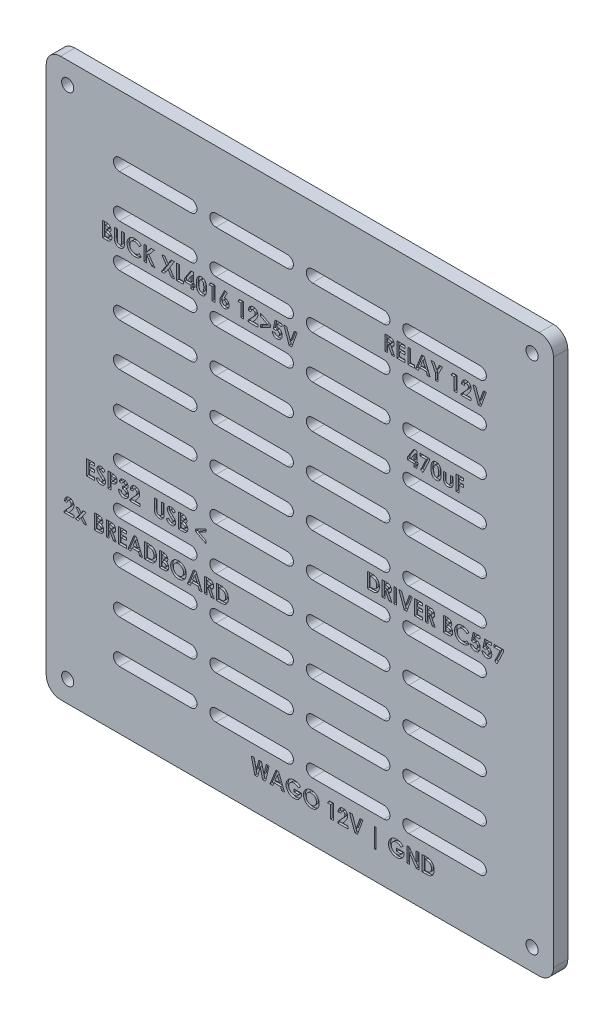
SolidWorks part; units mm, degrees
ref_plane "Front Plane" through (0, 0, 0) normal (0, 0, 1) x (1, 0, 0)
ref_plane "Top Plane" through (0, 0, 0) normal (0, 1, 0) x (1, 0, 0)
ref_plane "Right Plane" through (0, 0, 0) normal (1, 0, 0) x (0, 0, -1)
sketch "Sketch1" plane through (0, 0, 0) normal (0, 0, 1) x (1, 0, 0)
  line L0 (-67, 40) -> (67, 40)
  line L1 (71, 44) -> (71, 192)
  line L2 (67, 196) -> (-67, 196)
  line L3 (-71, 192) -> (-71, 44)
  arc A0 (-71, 44) -> (-67, 40) centre (-67, 44) ccw
  arc A1 (67, 40) -> (71, 44) centre (67, 44) ccw
  arc A2 (71, 192) -> (67, 196) centre (67, 192) ccw
  arc A3 (-67, 196) -> (-71, 192) centre (-67, 192) ccw
extrude "Plate" add sketch "Sketch1" along normal blind 4
sketch "Sketch2" plane through (0, 0, 0) normal (0, 0, 1) x (1, 0, 0)
  line L0 (-50.5, 58) -> (-30.5, 58) construction
  line L1 (-50.5, 59.7) -> (-30.5, 59.7)
  line L2 (-50.5, 56.3) -> (-30.5, 56.3)
  line L3 (-23.5, 58) -> (-3.5, 58) construction
  line L4 (-23.5, 59.7) -> (-3.5, 59.7)
  line L5 (-23.5, 56.3) -> (-3.5, 56.3)
  line L6 (3.5, 58) -> (23.5, 58) construction
  line L7 (3.5, 59.7) -> (23.5, 59.7)
  line L8 (3.5, 56.3) -> (23.5, 56.3)
  line L9 (30.5, 58) -> (50.5, 58) construction
  line L10 (30.5, 59.7) -> (50.5, 59.7)
  line L11 (30.5, 56.3) -> (50.5, 56.3)
  line L12 (-50.5, 70) -> (-30.5, 70) construction
  line L13 (-50.5, 71.7) -> (-30.5, 71.7)
  line L14 (-50.5, 68.3) -> (-30.5, 68.3)
  line L15 (-23.5, 70) -> (-3.5, 70) construction
  line L16 (-23.5, 71.7) -> (-3.5, 71.7)
  line L17 (-23.5, 68.3) -> (-3.5, 68.3)
  line L18 (3.5, 70) -> (23.5, 70) construction
  line L19 (3.5, 71.7) -> (23.5, 71.7)
  line L20 (3.5, 68.3) -> (23.5, 68.3)
  line L21 (30.5, 70) -> (50.5, 70) construction
  line L22 (30.5, 71.7) -> (50.5, 71.7)
  line L23 (30.5, 68.3) -> (50.5, 68.3)
  line L24 (-50.5, 82) -> (-30.5, 82) construction
  line L25 (-50.5, 83.7) -> (-30.5, 83.7)
  line L26 (-50.5, 80.3) -> (-30.5, 80.3)
  line L27 (-23.5, 82) -> (-3.5, 82) construction
  line L28 (-23.5, 83.7) -> (-3.5, 83.7)
  line L29 (-23.5, 80.3) -> (-3.5, 80.3)
  line L30 (3.5, 82) -> (23.5, 82) construction
  line L31 (3.5, 83.7) -> (23.5, 83.7)
  line L32 (3.5, 80.3) -> (23.5, 80.3)
  line L33 (30.5, 82) -> (50.5, 82) construction
  line L34 (30.5, 83.7) -> (50.5, 83.7)
  line L35 (30.5, 80.3) -> (50.5, 80.3)
  line L36 (-50.5, 94) -> (-30.5, 94) construction
  line L37 (-50.5, 95.7) -> (-30.5, 95.7)
  line L38 (-50.5, 92.3) -> (-30.5, 92.3)
  line L39 (-23.5, 94) -> (-3.5, 94) construction
  line L40 (-23.5, 95.7) -> (-3.5, 95.7)
  line L41 (-23.5, 92.3) -> (-3.5, 92.3)
  line L42 (3.5, 94) -> (23.5, 94) construction
  line L43 (3.5, 95.7) -> (23.5, 95.7)
  line L44 (3.5, 92.3) -> (23.5, 92.3)
  line L45 (30.5, 94) -> (50.5, 94) construction
  line L46 (30.5, 95.7) -> (50.5, 95.7)
  line L47 (30.5, 92.3) -> (50.5, 92.3)
  line L48 (-50.5, 106) -> (-30.5, 106) construction
  line L49 (-50.5, 107.7) -> (-30.5, 107.7)
  line L50 (-50.5, 104.3) -> (-30.5, 104.3)
  line L51 (-23.5, 106) -> (-3.5, 106) construction
  line L52 (-23.5, 107.7) -> (-3.5, 107.7)
  line L53 (-23.5, 104.3) -> (-3.5, 104.3)
  line L54 (3.5, 106) -> (23.5, 106) construction
  line L55 (3.5, 107.7) -> (23.5, 107.7)
  line L56 (3.5, 104.3) -> (23.5, 104.3)
  line L57 (30.5, 106) -> (50.5, 106) construction
  line L58 (30.5, 107.7) -> (50.5, 107.7)
  line L59 (30.5, 104.3) -> (50.5, 104.3)
  line L60 (-50.5, 118) -> (-30.5, 118) construction
  line L61 (-50.5, 119.7) -> (-30.5, 119.7)
  line L62 (-50.5, 116.3) -> (-30.5, 116.3)
  line L63 (-23.5, 118) -> (-3.5, 118) construction
  line L64 (-23.5, 119.7) -> (-3.5, 119.7)
  line L65 (-23.5, 116.3) -> (-3.5, 116.3)
  line L66 (3.5, 118) -> (23.5, 118) construction
  line L67 (3.5, 119.7) -> (23.5, 119.7)
  line L68 (3.5, 116.3) -> (23.5, 116.3)
  line L69 (30.5, 118) -> (50.5, 118) construction
  line L70 (30.5, 119.7) -> (50.5, 119.7)
  line L71 (30.5, 116.3) -> (50.5, 116.3)
  line L72 (-50.5, 130) -> (-30.5, 130) construction
  line L73 (-50.5, 131.7) -> (-30.5, 131.7)
  line L74 (-50.5, 128.3) -> (-30.5, 128.3)
  line L75 (-23.5, 130) -> (-3.5, 130) construction
  line L76 (-23.5, 131.7) -> (-3.5, 131.7)
  line L77 (-23.5, 128.3) -> (-3.5, 128.3)
  line L78 (3.5, 130) -> (23.5, 130) construction
  line L79 (3.5, 131.7) -> (23.5, 131.7)
  line L80 (3.5, 128.3) -> (23.5, 128.3)
  line L81 (30.5, 130) -> (50.5, 130) construction
  line L82 (30.5, 131.7) -> (50.5, 131.7)
  line L83 (30.5, 128.3) -> (50.5, 128.3)
  line L84 (-50.5, 142) -> (-30.5, 142) construction
  line L85 (-50.5, 143.7) -> (-30.5, 143.7)
  line L86 (-50.5, 140.3) -> (-30.5, 140.3)
  line L87 (-23.5, 142) -> (-3.5, 142) construction
  line L88 (-23.5, 143.7) -> (-3.5, 143.7)
  line L89 (-23.5, 140.3) -> (-3.5, 140.3)
  line L90 (3.5, 142) -> (23.5, 142) construction
  line L91 (3.5, 143.7) -> (23.5, 143.7)
  line L92 (3.5, 140.3) -> (23.5, 140.3)
  line L93 (30.5, 142) -> (50.5, 142) construction
  line L94 (30.5, 143.7) -> (50.5, 143.7)
  line L95 (30.5, 140.3) -> (50.5, 140.3)
  line L96 (-50.5, 154) -> (-30.5, 154) construction
  line L97 (-50.5, 155.7) -> (-30.5, 155.7)
  line L98 (-50.5, 152.3) -> (-30.5, 152.3)
  line L99 (-23.5, 154) -> (-3.5, 154) construction
  line L100 (-23.5, 155.7) -> (-3.5, 155.7)
  line L101 (-23.5, 152.3) -> (-3.5, 152.3)
  line L102 (3.5, 154) -> (23.5, 154) construction
  line L103 (3.5, 155.7) -> (23.5, 155.7)
  line L104 (3.5, 152.3) -> (23.5, 152.3)
  line L105 (30.5, 154) -> (50.5, 154) construction
  line L106 (30.5, 155.7) -> (50.5, 155.7)
  line L107 (30.5, 152.3) -> (50.5, 152.3)
  line L108 (-50.5, 166) -> (-30.5, 166) construction
  line L109 (-50.5, 167.7) -> (-30.5, 167.7)
  line L110 (-50.5, 164.3) -> (-30.5, 164.3)
  line L111 (-23.5, 166) -> (-3.5, 166) construction
  line L112 (-23.5, 167.7) -> (-3.5, 167.7)
  line L113 (-23.5, 164.3) -> (-3.5, 164.3)
  line L114 (3.5, 166) -> (23.5, 166) construction
  line L115 (3.5, 167.7) -> (23.5, 167.7)
  line L116 (3.5, 164.3) -> (23.5, 164.3)
  line L117 (30.5, 166) -> (50.5, 166) construction
  line L118 (30.5, 167.7) -> (50.5, 167.7)
  line L119 (30.5, 164.3) -> (50.5, 164.3)
  line L120 (-50.5, 178) -> (-30.5, 178) construction
  line L121 (-50.5, 179.7) -> (-30.5, 179.7)
  line L122 (-50.5, 176.3) -> (-30.5, 176.3)
  line L123 (-23.5, 178) -> (-3.5, 178) construction
  line L124 (-23.5, 179.7) -> (-3.5, 179.7)
  line L125 (-23.5, 176.3) -> (-3.5, 176.3)
  line L126 (3.5, 178) -> (23.5, 178) construction
  line L127 (3.5, 179.7) -> (23.5, 179.7)
  line L128 (3.5, 176.3) -> (23.5, 176.3)
  line L129 (30.5, 178) -> (50.5, 178) construction
  line L130 (30.5, 179.7) -> (50.5, 179.7)
  line L131 (30.5, 176.3) -> (50.5, 176.3)
  circle A0 centre (-65, 46) radius 1.7
  circle A1 centre (65, 46) radius 1.7
  circle A2 centre (-65, 190) radius 1.7
  circle A3 centre (65, 190) radius 1.7
  arc A4 (-50.5, 59.7) -> (-50.5, 56.3) centre (-50.5, 58) ccw
  arc A5 (-30.5, 56.3) -> (-30.5, 59.7) centre (-30.5, 58) ccw
  arc A6 (-23.5, 59.7) -> (-23.5, 56.3) centre (-23.5, 58) ccw
  arc A7 (-3.5, 56.3) -> (-3.5, 59.7) centre (-3.5, 58) ccw
  arc A8 (3.5, 59.7) -> (3.5, 56.3) centre (3.5, 58) ccw
  arc A9 (23.5, 56.3) -> (23.5, 59.7) centre (23.5, 58) ccw
  arc A10 (30.5, 59.7) -> (30.5, 56.3) centre (30.5, 58) ccw
  arc A11 (50.5, 56.3) -> (50.5, 59.7) centre (50.5, 58) ccw
  arc A12 (-50.5, 71.7) -> (-50.5, 68.3) centre (-50.5, 70) ccw
  arc A13 (-30.5, 68.3) -> (-30.5, 71.7) centre (-30.5, 70) ccw
  arc A14 (-23.5, 71.7) -> (-23.5, 68.3) centre (-23.5, 70) ccw
  arc A15 (-3.5, 68.3) -> (-3.5, 71.7) centre (-3.5, 70) ccw
  arc A16 (3.5, 71.7) -> (3.5, 68.3) centre (3.5, 70) ccw
  arc A17 (23.5, 68.3) -> (23.5, 71.7) centre (23.5, 70) ccw
  arc A18 (30.5, 71.7) -> (30.5, 68.3) centre (30.5, 70) ccw
  arc A19 (50.5, 68.3) -> (50.5, 71.7) centre (50.5, 70) ccw
  arc A20 (-50.5, 83.7) -> (-50.5, 80.3) centre (-50.5, 82) ccw
  arc A21 (-30.5, 80.3) -> (-30.5, 83.7) centre (-30.5, 82) ccw
  arc A22 (-23.5, 83.7) -> (-23.5, 80.3) centre (-23.5, 82) ccw
  arc A23 (-3.5, 80.3) -> (-3.5, 83.7) centre (-3.5, 82) ccw
  arc A24 (3.5, 83.7) -> (3.5, 80.3) centre (3.5, 82) ccw
  arc A25 (23.5, 80.3) -> (23.5, 83.7) centre (23.5, 82) ccw
  arc A26 (30.5, 83.7) -> (30.5, 80.3) centre (30.5, 82) ccw
  arc A27 (50.5, 80.3) -> (50.5, 83.7) centre (50.5, 82) ccw
  arc A28 (-50.5, 95.7) -> (-50.5, 92.3) centre (-50.5, 94) ccw
  arc A29 (-30.5, 92.3) -> (-30.5, 95.7) centre (-30.5, 94) ccw
  arc A30 (-23.5, 95.7) -> (-23.5, 92.3) centre (-23.5, 94) ccw
  arc A31 (-3.5, 92.3) -> (-3.5, 95.7) centre (-3.5, 94) ccw
  arc A32 (3.5, 95.7) -> (3.5, 92.3) centre (3.5, 94) ccw
  arc A33 (23.5, 92.3) -> (23.5, 95.7) centre (23.5, 94) ccw
  arc A34 (30.5, 95.7) -> (30.5, 92.3) centre (30.5, 94) ccw
  arc A35 (50.5, 92.3) -> (50.5, 95.7) centre (50.5, 94) ccw
  arc A36 (-50.5, 107.7) -> (-50.5, 104.3) centre (-50.5, 106) ccw
  arc A37 (-30.5, 104.3) -> (-30.5, 107.7) centre (-30.5, 106) ccw
  arc A38 (-23.5, 107.7) -> (-23.5, 104.3) centre (-23.5, 106) ccw
  arc A39 (-3.5, 104.3) -> (-3.5, 107.7) centre (-3.5, 106) ccw
  arc A40 (3.5, 107.7) -> (3.5, 104.3) centre (3.5, 106) ccw
  arc A41 (23.5, 104.3) -> (23.5, 107.7) centre (23.5, 106) ccw
  arc A42 (30.5, 107.7) -> (30.5, 104.3) centre (30.5, 106) ccw
  arc A43 (50.5, 104.3) -> (50.5, 107.7) centre (50.5, 106) ccw
  arc A44 (-50.5, 119.7) -> (-50.5, 116.3) centre (-50.5, 118) ccw
  arc A45 (-30.5, 116.3) -> (-30.5, 119.7) centre (-30.5, 118) ccw
  arc A46 (-23.5, 119.7) -> (-23.5, 116.3) centre (-23.5, 118) ccw
  arc A47 (-3.5, 116.3) -> (-3.5, 119.7) centre (-3.5, 118) ccw
  arc A48 (3.5, 119.7) -> (3.5, 116.3) centre (3.5, 118) ccw
  arc A49 (23.5, 116.3) -> (23.5, 119.7) centre (23.5, 118) ccw
  arc A50 (30.5, 119.7) -> (30.5, 116.3) centre (30.5, 118) ccw
  arc A51 (50.5, 116.3) -> (50.5, 119.7) centre (50.5, 118) ccw
  arc A52 (-50.5, 131.7) -> (-50.5, 128.3) centre (-50.5, 130) ccw
  arc A53 (-30.5, 128.3) -> (-30.5, 131.7) centre (-30.5, 130) ccw
  arc A54 (-23.5, 131.7) -> (-23.5, 128.3) centre (-23.5, 130) ccw
  arc A55 (-3.5, 128.3) -> (-3.5, 131.7) centre (-3.5, 130) ccw
  arc A56 (3.5, 131.7) -> (3.5, 128.3) centre (3.5, 130) ccw
  arc A57 (23.5, 128.3) -> (23.5, 131.7) centre (23.5, 130) ccw
  arc A58 (30.5, 131.7) -> (30.5, 128.3) centre (30.5, 130) ccw
  arc A59 (50.5, 128.3) -> (50.5, 131.7) centre (50.5, 130) ccw
  arc A60 (-50.5, 143.7) -> (-50.5, 140.3) centre (-50.5, 142) ccw
  arc A61 (-30.5, 140.3) -> (-30.5, 143.7) centre (-30.5, 142) ccw
  arc A62 (-23.5, 143.7) -> (-23.5, 140.3) centre (-23.5, 142) ccw
  arc A63 (-3.5, 140.3) -> (-3.5, 143.7) centre (-3.5, 142) ccw
  arc A64 (3.5, 143.7) -> (3.5, 140.3) centre (3.5, 142) ccw
  arc A65 (23.5, 140.3) -> (23.5, 143.7) centre (23.5, 142) ccw
  arc A66 (30.5, 143.7) -> (30.5, 140.3) centre (30.5, 142) ccw
  arc A67 (50.5, 140.3) -> (50.5, 143.7) centre (50.5, 142) ccw
  arc A68 (-50.5, 155.7) -> (-50.5, 152.3) centre (-50.5, 154) ccw
  arc A69 (-30.5, 152.3) -> (-30.5, 155.7) centre (-30.5, 154) ccw
  arc A70 (-23.5, 155.7) -> (-23.5, 152.3) centre (-23.5, 154) ccw
  arc A71 (-3.5, 152.3) -> (-3.5, 155.7) centre (-3.5, 154) ccw
  arc A72 (3.5, 155.7) -> (3.5, 152.3) centre (3.5, 154) ccw
  arc A73 (23.5, 152.3) -> (23.5, 155.7) centre (23.5, 154) ccw
  arc A74 (30.5, 155.7) -> (30.5, 152.3) centre (30.5, 154) ccw
  arc A75 (50.5, 152.3) -> (50.5, 155.7) centre (50.5, 154) ccw
  arc A76 (-50.5, 167.7) -> (-50.5, 164.3) centre (-50.5, 166) ccw
  arc A77 (-30.5, 164.3) -> (-30.5, 167.7) centre (-30.5, 166) ccw
  arc A78 (-23.5, 167.7) -> (-23.5, 164.3) centre (-23.5, 166) ccw
  arc A79 (-3.5, 164.3) -> (-3.5, 167.7) centre (-3.5, 166) ccw
  arc A80 (3.5, 167.7) -> (3.5, 164.3) centre (3.5, 166) ccw
  arc A81 (23.5, 164.3) -> (23.5, 167.7) centre (23.5, 166) ccw
  arc A82 (30.5, 167.7) -> (30.5, 164.3) centre (30.5, 166) ccw
  arc A83 (50.5, 164.3) -> (50.5, 167.7) centre (50.5, 166) ccw
  arc A84 (-50.5, 179.7) -> (-50.5, 176.3) centre (-50.5, 178) ccw
  arc A85 (-30.5, 176.3) -> (-30.5, 179.7) centre (-30.5, 178) ccw
  arc A86 (-23.5, 179.7) -> (-23.5, 176.3) centre (-23.5, 178) ccw
  arc A87 (-3.5, 176.3) -> (-3.5, 179.7) centre (-3.5, 178) ccw
  arc A88 (3.5, 179.7) -> (3.5, 176.3) centre (3.5, 178) ccw
  arc A89 (23.5, 176.3) -> (23.5, 179.7) centre (23.5, 178) ccw
  arc A90 (30.5, 179.7) -> (30.5, 176.3) centre (30.5, 178) ccw
  arc A91 (50.5, 176.3) -> (50.5, 179.7) centre (50.5, 178) ccw
  point P10 (-40.5, 58)
  point P15 (-13.5, 58)
  point P22 (13.5, 58)
  point P29 (40.5, 58)
  point P36 (-40.5, 70)
  point P43 (-13.5, 70)
  point P50 (13.5, 70)
  point P57 (40.5, 70)
  point P64 (-40.5, 82)
  point P71 (-13.5, 82)
  point P78 (13.5, 82)
  point P85 (40.5, 82)
  point P92 (-40.5, 94)
  point P99 (-13.5, 94)
  point P106 (13.5, 94)
  point P113 (40.5, 94)
  point P120 (-40.5, 106)
  point P127 (-13.5, 106)
  point P134 (13.5, 106)
  point P141 (40.5, 106)
  point P148 (-40.5, 118)
  point P155 (-13.5, 118)
  point P162 (13.5, 118)
  point P169 (40.5, 118)
  point P176 (-40.5, 130)
  point P183 (-13.5, 130)
  point P190 (13.5, 130)
  point P197 (40.5, 130)
  point P204 (-40.5, 142)
  point P211 (-13.5, 142)
  point P218 (13.5, 142)
  point P225 (40.5, 142)
  point P232 (-40.5, 154)
  point P239 (-13.5, 154)
  point P246 (13.5, 154)
  point P253 (40.5, 154)
  point P260 (-40.5, 166)
  point P267 (-13.5, 166)
  point P274 (13.5, 166)
  point P281 (40.5, 166)
  point P288 (-40.5, 178)
  point P295 (-13.5, 178)
  point P302 (13.5, 178)
  point P309 (40.5, 178)
  point P316 (0, 0)
extrude "Mounting slots" cut sketch "Sketch2" along normal through all
ref_plane "P1_Front_4" through (0, 0, 4) normal (0, 0, 1) x (1, 0, 0)
sketch "Sketch3" plane through (0, 0, 4) normal (0, 0, 1) x (1, 0, 0)
  text T0 "BUCK XL4016 12>5V" font "Century Gothic" height 4.2
  text T1 "RELAY 12V" font "Century Gothic" height 4.2
  text T2 "470uF" font "Century Gothic" height 4.2
  text T3 "ESP32  USB <" font "Century Gothic" height 4.2
  text T4 "2x BREADBOARD" font "Century Gothic" height 4.2
  text T5 "DRIVER BC557" font "Century Gothic" height 4.2
  text T6 "WAGO 12V | GND" font "Century Gothic" height 4.2
extrude "Zone labels" cut sketch "Sketch3" against normal blind 0.6
